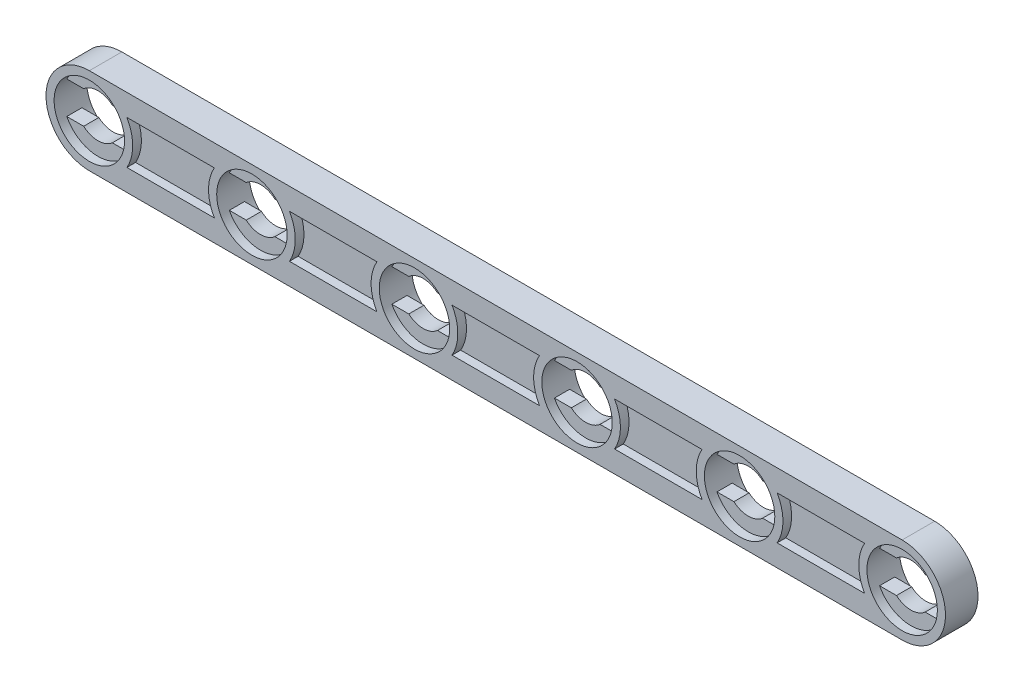
SolidWorks part; units mm, degrees
ref_plane "前视基准面" through (0, 0, 0) normal (0, 0, 1) x (1, 0, 0)
ref_plane "上视基准面" through (0, 0, 0) normal (0, 1, 0) x (1, 0, 0)
ref_plane "右视基准面" through (0, 0, 0) normal (1, 0, 0) x (0, 0, -1)
sketch "草图1" plane through (0, 0, 0) normal (0, 0, 1) x (1, 0, 0)
  line L1 (0, 4) -> (75, 4)
  line L3 (0, -4) -> (75, -4)
  arc A0 (0, 4) -> (0, -4) centre (0, 0) ccw
  arc A1 (75, -4) -> (75, 4) centre (75, 0) ccw
extrude "凸台-拉伸1" add sketch "草图1" against normal blind 3
sketch "草图2" plane through (0, 0, 0) normal (0, 0, 1) x (1, 0, 0)
  line L0 (1.3229, -1.5) -> (2.8831, -1.5)
  line L1 (-2.8831, -1.5) -> (-1.3229, -1.5)
  line L2 (1.3229, 1.5) -> (2.8831, 1.5)
  line L3 (-2.8831, 1.5) -> (-1.3229, 1.5)
  arc A0 (1.3229, 1.5) -> (-1.3229, 1.5) centre (0, 0) ccw
  arc A1 (-2.8831, 1.5) -> (-2.8831, -1.5) centre (0, 0) ccw
  arc A3 (2.8831, -1.5) -> (2.8831, 1.5) centre (0, 0) ccw
  arc A4 (-1.3229, -1.5) -> (1.3229, -1.5) centre (0, 0) ccw
extrude "切除-拉伸1" cut sketch "草图2" against normal up to next
sketch "草图3" plane through (0, 0, 0) normal (0, 0, 1) x (1, 0, 0)
  circle A1 centre (0, 0) radius 3.25
extrude "切除-拉伸2" cut sketch "草图3" against normal blind 0.8
extrude "切除-拉伸3" cut sketch "草图3<2>" along normal blind 0.8 from offset 3 offset against normal yes
sketch "草图3<2>" plane through (0, 0, 0) normal (0, 0, 1) x (1, 0, 0) same geometry as "草图3"
sketch "草图4" plane through (0, 0, 0) normal (0, 0, 1) x (1, 0, 0)
  line L1 (3.4641, 2) -> (11.5359, 2)
  line L3 (3.4641, -2) -> (11.5359, -2)
  arc A0 (11.5359, 2) -> (11.5359, -2) centre (15, 0) ccw
  arc A2 (3.4641, -2) -> (3.4641, 2) centre (0, 0) ccw
extrude "切除-拉伸4" cut sketch "草图4" against normal blind 0.8
sketch "草图5" plane through (0, 0, -3) normal (0, 0, -1) x (-1, 0, 0)
  line L1 (-4, -2) -> (-11, -2)
  line L2 (-4, -2) -> (-4, 2)
  line L3 (-4, 2) -> (-11, 2)
  line L4 (-11, -2) -> (-11, 2)
extrude "切除-拉伸6" cut sketch "草图5" against normal blind 0.8
ref_plane "基准面1" through (7.5, 0, 0) normal (1, 0, 0) x (0, 0, -1)
mirror "镜向1" about plane through (7.5, 0, 0) normal (1, 0, 0) of "切除-拉伸3", "切除-拉伸2", "切除-拉伸1"
ref_plane "基准面2" through (22.5, 0, 0) normal (1, 0, 0) x (0, 0, -1)
ref_plane "基准面3" through (15, 0, 0) normal (1, 0, 0) x (0, 0, -1)
mirror "镜向3" about plane through (15, 0, 0) normal (1, 0, 0) of "切除-拉伸6", "切除-拉伸4"
mirror "镜向4" about plane through (22.5, 0, 0) normal (1, 0, 0) of "切除-拉伸4", "切除-拉伸6"
ref_plane "基准面6" through (37.5, 0, 0) normal (1, 0, 0) x (0, 0, -1)
mirror "镜向7" about plane through (15, 0, 0) normal (1, 0, 0) of "切除-拉伸3", "切除-拉伸2", "切除-拉伸1"
mirror "镜向8" about plane through (37.5, 0, 0) normal (1, 0, 0) of "镜向7", "镜向3", "镜向1", "切除-拉伸6", "切除-拉伸4", "切除-拉伸3", "切除-拉伸2", "切除-拉伸1"
